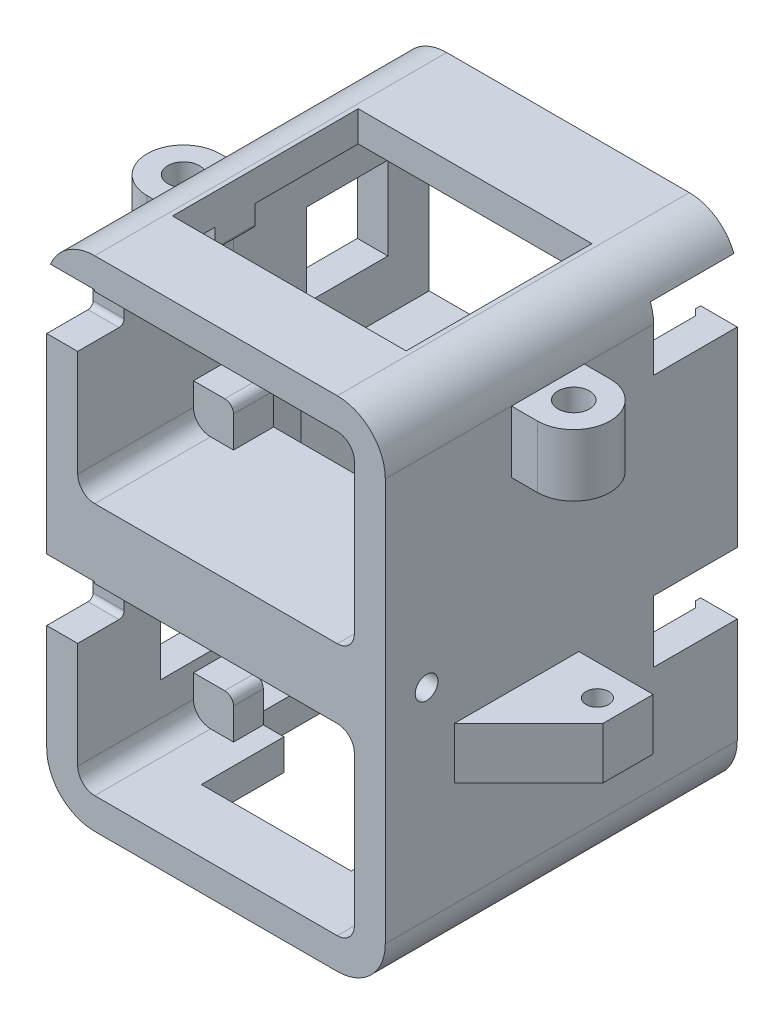
SolidWorks part; units mm, degrees
ref_plane "前视基准面" through (0, 0, 0) normal (0, 0, 1) x (1, 0, 0)
ref_plane "上视基准面" through (0, 0, 0) normal (0, 1, 0) x (1, 0, 0)
ref_plane "右视基准面" through (0, 0, 0) normal (1, 0, 0) x (0, 0, -1)
other "Configuration Table"
sketch "草图2" plane through (0, 0, 0) normal (0, 0, 1) x (1, 0, 0)
  line L20 (13.4, -7.25) -> (13.4, 7.25)
  line L21 (11.75, 8.9) -> (-16.9, 8.9)
  line L22 (-16.9, 8.9) -> (-16.9, 3.2)
  line L23 (-16.9, 3.2) -> (-13.4, 3.2)
  line L24 (-13.4, 3.2) -> (-13.4, -7.25)
  line L25 (-11.75, -8.9) -> (-3.85, -8.9)
  line L26 (-3.85, -8.9) -> (-3.85, -7.9)
  line L27 (-3.85, -7.9) -> (3.85, -7.9)
  line L28 (3.85, -7.9) -> (3.85, -8.9)
  line L29 (3.85, -8.9) -> (11.75, -8.9)
  line L40 (13.4, -7.25) -> (13.4, 7.25)
  line L41 (11.75, 8.9) -> (-16.9, 8.9)
  line L42 (-16.9, 8.9) -> (-16.9, 3.2)
  line L43 (-16.9, 3.2) -> (-13.4, 3.2)
  line L44 (-13.4, 3.2) -> (-13.4, -7.25)
  line L45 (-11.75, -8.9) -> (-3.85, -8.9)
  line L49 (3.85, -8.9) -> (11.75, -8.9)
  line L50 (-3.85, 15.6) -> (3.85, 15.6)
  line L51 (-3.85, -8.9) -> (3.85, -8.9)
  line L52 (-3.85, 12.6) -> (3.85, 12.6)
  line L53 (3.85, 12.6) -> (11.75, 12.6)
  line L54 (16.4, 17.25) -> (16.4, 31.75)
  line L55 (11.75, 36.4) -> (-19.9, 36.4)
  line L56 (-19.9, 36.4) -> (-19.9, 24.7)
  line L57 (-19.9, 24.7) -> (-16.4, 24.7)
  line L58 (-16.4, 24.7) -> (-16.4, 17.25)
  line L59 (-11.75, 12.6) -> (-3.85, 12.6)
  line L70 (13.4, 17.25) -> (13.4, 31.75)
  line L71 (11.75, 33.4) -> (-16.9, 33.4)
  line L72 (-16.9, 33.4) -> (-16.9, 27.7)
  line L73 (-16.9, 27.7) -> (-13.4, 27.7)
  line L74 (-13.4, 27.7) -> (-13.4, 17.25)
  line L75 (-11.75, 15.6) -> (-3.85, 15.6)
  line L76 (-3.85, 15.6) -> (-3.85, 16.6)
  line L77 (-3.85, 16.6) -> (3.85, 16.6)
  line L78 (3.85, 16.6) -> (3.85, 15.6)
  line L79 (3.85, 15.6) -> (11.75, 15.6)
  line L80 (13.4, 17.25) -> (13.4, 31.75)
  line L81 (11.75, 33.4) -> (-16.9, 33.4)
  line L82 (-16.9, 33.4) -> (-16.9, 27.7)
  line L83 (-16.9, 27.7) -> (-13.4, 27.7)
  line L84 (-13.4, 27.7) -> (-13.4, 17.25)
  line L85 (-11.75, 15.6) -> (-3.85, 15.6)
  line L89 (3.85, 15.6) -> (11.75, 15.6)
  line L90 (16.4, -7.25) -> (16.4, 7.25)
  line L91 (11.75, 11.9) -> (-19.9, 11.9)
  line L92 (-19.9, 11.9) -> (-19.9, 0.2)
  line L93 (-19.9, 0.2) -> (-16.4, 0.2)
  line L94 (-16.4, 0.2) -> (-16.4, -7.25)
  line L95 (-11.75, -11.9) -> (-3.85, -11.9)
  line L96 (-3.85, -11.9) -> (3.85, -11.9)
  line L97 (3.85, -11.9) -> (11.75, -11.9)
  line L98 (-16.4, 0.2) -> (-16.4, 3.2)
  line L99 (-16.4, 17.25) -> (-16.4, 11.9)
  line L100 (16.4, 17.25) -> (16.4, 7.25)
  line L101 (-16.9, 33.4) -> (-19.9, 33.4)
  line L102 (-16.9, 27.7) -> (-19.9, 27.7)
  line L103 (-16.9, 8.9) -> (-19.9, 8.9)
  line L104 (-16.4, 24.7) -> (-16.4, 27.7)
  line L105 (-16.4, 36.4) -> (-16.4, 33.4)
  line L106 (-16.4, 11.9) -> (-16.4, 8.9)
  line L107 (-16.4, 33.4) -> (-16.4, 27.7)
  line L108 (-16.4, 8.9) -> (-16.4, 3.2)
  line L109 (-13.4, 27.7) -> (-13.4, 33.4)
  line L110 (-13.4, 3.2) -> (-13.4, 8.9)
  arc A1 (-11.75, 11.9) -> (-16.4, 7.25) centre (-11.75, 7.25) ccw
  arc A2 (-11.75, 8.9) -> (-13.4, 7.25) centre (-11.75, 7.25) ccw
  arc A3 (-11.75, 8.9) -> (-13.4, 7.25) centre (-11.75, 7.25) ccw
  arc A6 (13.4, 7.25) -> (11.75, 8.9) centre (11.75, 7.25) ccw
  arc A7 (-13.4, -7.25) -> (-11.75, -8.9) centre (-11.75, -7.25) ccw
  arc A8 (11.75, -8.9) -> (13.4, -7.25) centre (11.75, -7.25) ccw
  arc A12 (13.4, 7.25) -> (11.75, 8.9) centre (11.75, 7.25) ccw
  arc A13 (-13.4, -7.25) -> (-11.75, -8.9) centre (-11.75, -7.25) ccw
  arc A14 (11.75, -8.9) -> (13.4, -7.25) centre (11.75, -7.25) ccw
  arc A15 (11.75, 12.6) -> (16.4, 17.25) centre (11.75, 17.25) ccw
  arc A16 (16.4, 31.75) -> (11.75, 36.4) centre (11.75, 31.75) ccw
  arc A17 (-16.4, 17.25) -> (-11.75, 12.6) centre (-11.75, 17.25) ccw
  arc A21 (13.4, 31.75) -> (11.75, 33.4) centre (11.75, 31.75) ccw
  arc A22 (-13.4, 17.25) -> (-11.75, 15.6) centre (-11.75, 17.25) ccw
  arc A23 (11.75, 15.6) -> (13.4, 17.25) centre (11.75, 17.25) ccw
  arc A24 (13.4, 31.75) -> (11.75, 33.4) centre (11.75, 31.75) ccw
  arc A25 (-13.4, 17.25) -> (-11.75, 15.6) centre (-11.75, 17.25) ccw
  arc A26 (11.75, 15.6) -> (13.4, 17.25) centre (11.75, 17.25) ccw
  arc A27 (16.4, 7.25) -> (11.75, 11.9) centre (11.75, 7.25) ccw
  arc A28 (-16.4, -7.25) -> (-11.75, -11.9) centre (-11.75, -7.25) ccw
  arc A29 (11.75, -11.9) -> (16.4, -7.25) centre (11.75, -7.25) ccw
  arc A31 (-11.75, 36.4) -> (-16.4, 31.75) centre (-11.75, 31.75) ccw
  arc A32 (-11.75, 33.4) -> (-13.4, 31.75) centre (-11.75, 31.75) ccw
  arc A33 (-11.75, 33.4) -> (-13.4, 31.75) centre (-11.75, 31.75) ccw
  dimension "D3" = 3
  dimension "D4" = 3
  dimension "D5" = 0.1
  dimension "D6" = 3
  dimension "D7" = 0.1
  dimension "D8" = 3
extrude "凸台-拉伸2" add sketch "草图2" against normal up to surface (11.22 mm away)
sketch "草图3" plane through (0, 0, -11.22) normal (0, 0, -1) x (-1, 0, 0)
  line L0 (11.75, -8.9) -> (-11.75, -8.9) construction
  line L2 (-11.75, 8.9) -> (11.75, 8.9) construction
  line L3 (11.75, -8.9) -> (-11.75, -8.9)
  line L4 (16.4, -7.25) -> (16.4, 31.75)
  line L5 (11.75, 36.4) -> (-11.75, 36.4)
  line L6 (-16.4, 31.75) -> (-16.4, -7.25)
  line L7 (-11.75, -11.9) -> (11.75, -11.9)
  line L12 (16.4, -7.25) -> (16.4, 31.75)
  line L13 (11.75, 36.4) -> (-11.75, 36.4)
  line L14 (-16.4, 31.75) -> (-16.4, -7.25)
  line L16 (-11.75, -11.9) -> (11.75, -11.9)
  line L20 (-13.4, -7.25) -> (-13.4, 7.25)
  line L21 (-11.75, 33.4) -> (11.75, 33.4) construction
  line L22 (-13.4, 17.25) -> (-13.4, 31.75) construction
  line L23 (-9.52, -8.6) -> (-9.52, -5.87)
  line L24 (-10.37, -5.02) -> (-13.1, -5.02)
  line L25 (-13.1, -5.02) -> (-13.1, -7.25)
  line L26 (-11.75, -8.6) -> (-9.52, -8.6)
  line L27 (-9.52, -8.6) -> (-9.52, -5.87)
  line L28 (-10.37, -5.02) -> (-13.1, -5.02)
  line L32 (11.75, 15.6) -> (-11.75, 15.6) construction
  line L33 (-11.75, 33.4) -> (11.75, 33.4)
  line L34 (-13.4, 17.25) -> (-13.4, 31.75)
  line L36 (11.75, 15.6) -> (-11.75, 15.6)
  line L38 (13.4, 7.25) -> (13.4, -7.25) construction
  line L39 (13.1, -5.02) -> (10.37, -5.02)
  line L40 (9.52, -5.87) -> (9.52, -8.6)
  line L41 (9.52, -8.6) -> (11.75, -8.6)
  line L42 (13.1, -7.25) -> (13.1, -5.02)
  line L43 (13.1, -5.02) -> (10.37, -5.02)
  line L44 (9.52, -5.87) -> (9.52, -8.6)
  line L47 (13.4, 7.25) -> (13.4, -7.25)
  line L48 (-11.75, 8.9) -> (11.75, 8.9) construction
  line L49 (-9.52, 15.75) -> (-9.52, 18.63)
  line L50 (-10.37, 19.48) -> (-13.25, 19.48)
  line L51 (-13.1, 6.82) -> (-11.67, 6.82)
  line L52 (-11.32, 7.17) -> (-11.32, 8.6)
  line L53 (-11.32, 8.6) -> (-11.75, 8.6)
  line L54 (-13.1, 7.25) -> (-13.1, 6.82)
  line L55 (-13.1, 6.82) -> (-11.67, 6.82)
  line L56 (-11.32, 7.17) -> (-11.32, 8.6)
  line L59 (-13.1, 6.82) -> (-13.4, 6.82)
  line L60 (-13.4, -7.25) -> (-13.4, 7.25) construction
  line L61 (-9.52, 15.6) -> (-9.52, 18.63)
  line L62 (-10.37, 19.48) -> (-13.4, 19.48)
  line L63 (11.32, 8.6) -> (11.32, 7.17)
  line L64 (11.67, 6.82) -> (13.1, 6.82)
  line L65 (13.1, 6.82) -> (13.1, 7.25)
  line L66 (11.75, 8.6) -> (11.32, 8.6)
  line L67 (11.32, 8.9) -> (11.32, 7.17)
  line L68 (11.67, 6.82) -> (13.4, 6.82)
  line L71 (-11.75, 8.9) -> (11.75, 8.9)
  line L73 (-13.25, 31.32) -> (-11.67, 31.32)
  line L74 (-11.32, 31.67) -> (-11.32, 33.25)
  line L75 (-13.25, 31.32) -> (-11.67, 31.32)
  line L76 (-11.32, 31.67) -> (-11.32, 33.25)
  line L79 (11.67, 31.32) -> (13.25, 31.32)
  line L80 (11.32, 33.25) -> (11.32, 31.67)
  line L81 (11.67, 31.32) -> (13.4, 31.32)
  line L82 (11.32, 33.25) -> (11.32, 31.67)
  line L83 (-13.25, 31.32) -> (-13.4, 31.32)
  line L84 (-11.32, 33.25) -> (-11.32, 33.4)
  line L85 (9.52, 18.63) -> (9.52, 15.75)
  line L86 (13.25, 19.48) -> (10.37, 19.48)
  line L87 (9.52, 18.63) -> (9.52, 15.6)
  line L88 (13.4, 19.48) -> (10.37, 19.48)
  line L89 (11.32, 33.25) -> (11.32, 33.4)
  line L90 (-11.32, 8.6) -> (-11.32, 8.9)
  line L91 (13.4, 31.75) -> (13.4, 17.25) construction
  line L92 (13.4, 31.75) -> (13.4, 17.25)
  line L93 (-13.1, -5.02) -> (-13.4, -5.02)
  line L94 (-9.52, -8.6) -> (-9.52, -8.9)
  line L95 (9.52, -8.6) -> (9.52, -8.9)
  line L96 (13.1, -5.02) -> (13.4, -5.02)
  arc A0 (-13.4, -7.25) -> (-11.75, -8.9) centre (-11.75, -7.25) ccw construction
  arc A1 (11.75, -8.9) -> (13.4, -7.25) centre (11.75, -7.25) ccw construction
  arc A2 (-11.75, 8.9) -> (-13.4, 7.25) centre (-11.75, 7.25) ccw construction
  arc A3 (11.75, -11.9) -> (16.4, -7.25) centre (11.75, -7.25) ccw
  arc A4 (-11.75, 36.4) -> (-16.4, 31.75) centre (-11.75, 31.75) ccw
  arc A5 (-16.4, -7.25) -> (-11.75, -11.9) centre (-11.75, -7.25) ccw
  arc A6 (11.75, -11.9) -> (16.4, -7.25) centre (11.75, -7.25) ccw
  arc A9 (-11.75, 36.4) -> (-16.4, 31.75) centre (-11.75, 31.75) ccw
  arc A10 (-9.52, -5.87) -> (-10.37, -5.02) centre (-10.37, -5.87) ccw
  arc A11 (-13.1, -7.25) -> (-11.75, -8.6) centre (-11.75, -7.25) ccw
  arc A12 (-9.52, -5.87) -> (-10.37, -5.02) centre (-10.37, -5.87) ccw
  arc A14 (-16.4, -7.25) -> (-11.75, -11.9) centre (-11.75, -7.25) ccw
  arc A15 (-13.4, -7.25) -> (-11.75, -8.9) centre (-11.75, -7.25) ccw
  arc A16 (11.75, -8.9) -> (13.4, -7.25) centre (11.75, -7.25) ccw
  arc A17 (-11.75, 8.9) -> (-13.4, 7.25) centre (-11.75, 7.25) ccw
  arc A18 (10.37, -5.02) -> (9.52, -5.87) centre (10.37, -5.87) ccw
  arc A19 (11.75, -8.6) -> (13.1, -7.25) centre (11.75, -7.25) ccw
  arc A20 (10.37, -5.02) -> (9.52, -5.87) centre (10.37, -5.87) ccw
  arc A22 (-11.75, 33.4) -> (-13.4, 31.75) centre (-11.75, 31.75) ccw construction
  arc A23 (11.75, 15.6) -> (13.4, 17.25) centre (11.75, 17.25) ccw construction
  arc A24 (-11.67, 6.82) -> (-11.32, 7.17) centre (-11.67, 7.17) ccw
  arc A25 (-11.75, 8.6) -> (-13.1, 7.25) centre (-11.75, 7.25) ccw
  arc A26 (-11.67, 6.82) -> (-11.32, 7.17) centre (-11.67, 7.17) ccw
  arc A28 (-13.4, 17.25) -> (-11.75, 15.6) centre (-11.75, 17.25) ccw construction
  arc A29 (-11.75, 33.4) -> (-13.4, 31.75) centre (-11.75, 31.75) ccw
  arc A30 (11.32, 7.17) -> (11.67, 6.82) centre (11.67, 7.17) ccw
  arc A31 (13.1, 7.25) -> (11.75, 8.6) centre (11.75, 7.25) ccw
  arc A32 (11.32, 7.17) -> (11.67, 6.82) centre (11.67, 7.17) ccw
  arc A34 (11.75, 15.6) -> (13.4, 17.25) centre (11.75, 17.25) ccw
  arc A35 (-13.4, 17.25) -> (-11.75, 15.6) centre (-11.75, 17.25) ccw
  arc A36 (13.4, 7.25) -> (11.75, 8.9) centre (11.75, 7.25) ccw construction
  arc A37 (13.4, 7.25) -> (11.75, 8.9) centre (11.75, 7.25) ccw
  arc A38 (-9.52, 18.63) -> (-10.37, 19.48) centre (-10.37, 18.63) ccw
  arc A39 (-9.52, 18.63) -> (-10.37, 19.48) centre (-10.37, 18.63) ccw
  arc A41 (-11.67, 31.32) -> (-11.32, 31.67) centre (-11.67, 31.67) ccw
  arc A42 (-11.67, 31.32) -> (-11.32, 31.67) centre (-11.67, 31.67) ccw
  arc A44 (11.32, 31.67) -> (11.67, 31.32) centre (11.67, 31.67) ccw
  arc A45 (11.32, 31.67) -> (11.67, 31.32) centre (11.67, 31.67) ccw
  arc A46 (13.4, 31.75) -> (11.75, 33.4) centre (11.75, 31.75) ccw construction
  arc A47 (10.37, 19.48) -> (9.52, 18.63) centre (10.37, 18.63) ccw
  arc A48 (10.37, 19.48) -> (9.52, 18.63) centre (10.37, 18.63) ccw
  arc A49 (13.4, 31.75) -> (11.75, 33.4) centre (11.75, 31.75) ccw
  arc A52 (16.4, 31.75) -> (11.75, 36.4) centre (11.75, 31.75) ccw
  arc A53 (16.4, 31.75) -> (11.75, 36.4) centre (11.75, 31.75) ccw
  dimension "D7" = 0.1
  dimension "D9" = 0.1
extrude "凸台-拉伸3" add sketch "草图3" along normal up to surface (3.88 mm away)
sketch "草图4" plane through (-16.4, 0, 0) normal (-1, 0, 0) x (0, 0, 1)
  line L8 (0.3, 9.05) -> (-4, 9.05)
  line L9 (-4.5, 8.55) -> (-4.5, 3.55)
  line L10 (-4, 3.05) -> (0.3, 3.05)
  line L11 (0.3, 3.05) -> (0.3, 9.05)
  line L12 (0.3, 9.05) -> (-4, 9.05)
  line L13 (-4.5, 8.55) -> (-4.5, 3.55)
  line L14 (-4, 3.05) -> (0.3, 3.05)
  line L15 (0.3, 3.05) -> (0.3, 9.05)
  line L20 (0.3, 33.55) -> (-4, 33.55)
  line L21 (-4.5, 33.05) -> (-4.5, 28.05)
  line L22 (-4, 27.55) -> (0.3, 27.55)
  line L23 (0.3, 27.55) -> (0.3, 33.55)
  line L24 (0.3, 33.55) -> (-4, 33.55)
  line L25 (-4.5, 33.05) -> (-4.5, 28.05)
  line L26 (-4, 27.55) -> (0.3, 27.55)
  line L27 (0.3, 27.55) -> (0.3, 33.55)
  arc A4 (-4, 9.05) -> (-4.5, 8.55) centre (-4, 8.55) ccw
  arc A5 (-4.5, 3.55) -> (-4, 3.05) centre (-4, 3.55) ccw
  arc A6 (-4, 9.05) -> (-4.5, 8.55) centre (-4, 8.55) ccw
  arc A7 (-4.5, 3.55) -> (-4, 3.05) centre (-4, 3.55) ccw
  arc A10 (-4, 33.55) -> (-4.5, 33.05) centre (-4, 33.05) ccw
  arc A11 (-4.5, 28.05) -> (-4, 27.55) centre (-4, 28.05) ccw
  arc A12 (-4, 33.55) -> (-4.5, 33.05) centre (-4, 33.05) ccw
  arc A13 (-4.5, 28.05) -> (-4, 27.55) centre (-4, 28.05) ccw
  dimension "D2" = 0.15
  dimension "D1" = 0.15
extrude "切除-拉伸1" cut sketch "草图4" against normal blind 4.65
ref_plane "基准面1" through (0, 31.75, 0) normal (0, 1, 0) x (1, 0, 0)
sketch "草图8" plane through (0, 31.75, 0) normal (0, 1, 0) x (1, 0, 0)
  line L0 (18.9, 12.23) -> (15.375, 12.23)
  line L1 (15.375, 12.23) -> (15.375, 15.755)
  line L2 (16.4, 15.1) -> (16.4, 0) construction
  line L3 (-12.113, 15.755) -> (15.375, 15.755) construction
  line L4 (9.73, 15.91) -> (-9.73, 15.91) construction
  line L5 (-9.73, 15.6) -> (9.73, 15.6) construction
  line L9 (18.9, 19.28) -> (15.375, 19.28)
  line L10 (15.375, 15.755) -> (15.375, 19.28)
  circle A2 centre (18.9, 15.755) radius 1.525
  circle A3 centre (18.9, 15.755) radius 3.525
  point P16 (18.9, 19.28)
  point P17 (15.2716, 15.755)
  dimension "D1" = 3.05
  dimension "D3" = 2.5
  dimension "D2" = 2
extrude "凸台-拉伸5" add sketch "草图8" against normal blind 6 contours A3 A2 | A3 L9 L10 | A3 L1 L0
mirror "镜向1" about plane through (0, 0, 0) normal (1, 0, 0) of "凸台-拉伸5"
sketch "草图9" plane through (0, 0, -15.1) normal (0, 0, -1) x (-1, 0, 0)
  line L0 (-11.32, 33.4) -> (11.32, 33.4) construction
  line L1 (-11.32, 33.4) -> (11.32, 33.4)
  line L2 (-11.32, 33.4) -> (-11.32, 36.4)
  line L3 (-11.32, 36.4) -> (11.32, 36.4)
  line L4 (11.32, 33.4) -> (11.32, 36.4)
  line L5 (11.75, 36.4) -> (-11.75, 36.4) construction
  line L6 (-11.32, 31.67) -> (-11.32, 33.4) construction
  line L7 (11.32, 33.4) -> (11.32, 31.67) construction
extrude "切除-拉伸3" cut sketch "草图9" against normal blind 8
sketch "草图10" plane through (0, 0, -15.1) normal (0, 0, -1) x (-1, 0, 0)
  line L0 (-11.75, -11.9) -> (11.75, -11.9) construction
  line L1 (-10.73, -11.9) -> (10.73, -11.9)
  line L2 (-10.73, -11.9) -> (-10.73, -5.02)
  line L3 (-10.73, -5.02) -> (10.73, -5.02)
  line L4 (10.73, -11.9) -> (10.73, -5.02)
  line L5 (13.4, -5.02) -> (10.37, -5.02) construction
  line L6 (-9.73, 23.6695) -> (-9.73, 22.7695) construction
  line L7 (9.73, 71.4195) -> (9.73, -46.2805) construction
  dimension "D1" = 1
  dimension "D2" = 1
extrude "切除-拉伸4" cut sketch "草图10" against normal blind 1
sketch "草图12" plane through (-16.4, 0, 0) normal (-1, 0, 0) x (0, 0, 1)
  circle A0 centre (-4, 12.25) radius 1.1
  dimension "D1" = 2.2
extrude "切除-拉伸5" cut sketch "草图12" against normal blind 8
sketch "草图13" plane through (16.4, 0, 0) normal (1, 0, 0) x (0, 0, -1)
  circle A0 centre (4, 12.25) radius 1.1
  dimension "D1" = 2.2
extrude "切除-拉伸6" cut sketch "草图13" against normal blind 8
sketch "草图14" plane through (0, 0, -15.1) normal (0, 0, -1) x (-1, 0, 0)
  line L0 (-9.52, 18.63) -> (-16.4, 18.63)
  line L1 (-10.37, 19.48) -> (-13.4, 19.48) construction
  line L2 (-16.4, 8.95) -> (16.4, 8.95)
  line L3 (-9.52, 18.63) -> (16.4, 18.63)
  line L4 (-11.32, 8.9) -> (11.32, 8.9) construction
  line L6 (9.88, -46.4305) -> (9.88, 71.4899)
  line L7 (-9.88, -46.4305) -> (9.88, -46.4305)
  line L8 (-9.88, 71.4899) -> (-9.88, -46.4305)
  line L9 (9.88, -46.4305) -> (9.88, 71.4899)
  line L10 (-9.88, -46.4305) -> (9.88, -46.4305)
  line L11 (-9.88, 71.4899) -> (-9.88, -46.4305)
  line L19 (16.4, 3.05) -> (13.4, 3.05)
  line L20 (16.4, -7.25) -> (16.4, 3.05)
  line L21 (-11.75, -11.9) -> (11.75, -11.9)
  line L22 (-16.4, 31.75) -> (-16.4, -7.25)
  line L23 (11.75, 36.4) -> (-11.75, 36.4)
  line L24 (11.75, 33.55) -> (16.0375, 33.55)
  line L25 (11.75, 33.4) -> (11.75, 33.55)
  line L26 (-11.75, 33.4) -> (11.75, 33.4)
  line L27 (-13.4, 17.25) -> (-13.4, 31.75)
  line L28 (11.75, 15.6) -> (-11.75, 15.6)
  line L29 (13.4, 27.55) -> (13.4, 17.25)
  line L30 (16.4, 27.55) -> (13.4, 27.55)
  line L31 (16.4, 9.05) -> (16.4, 27.55)
  line L32 (11.75, 9.05) -> (16.4, 9.05)
  line L33 (11.75, 8.9) -> (11.75, 9.05)
  line L34 (-11.75, 8.9) -> (11.75, 8.9)
  line L35 (-13.4, -7.25) -> (-13.4, 7.25)
  line L36 (11.75, -8.9) -> (-11.75, -8.9)
  line L37 (13.4, 3.05) -> (13.4, -7.25)
  line L39 (16.4, -7.25) -> (16.4, 9.05)
  line L40 (-11.75, -11.9) -> (11.75, -11.9)
  line L41 (-16.4, 31.75) -> (-16.4, -7.25)
  line L42 (11.75, 36.4) -> (-11.75, 36.4)
  line L50 (16.4, 9.05) -> (16.4, 31.75)
  arc A2 (9.88, 71.4899) -> (-9.88, 71.4899) centre (0, 59.6448) ccw
  arc A3 (9.88, 71.4899) -> (-9.88, 71.4899) centre (0, 59.6448) ccw
  arc A10 (11.75, -11.9) -> (16.4, -7.25) centre (11.75, -7.25) ccw
  arc A11 (-16.4, -7.25) -> (-11.75, -11.9) centre (-11.75, -7.25) ccw
  arc A12 (-11.75, 36.4) -> (-16.4, 31.75) centre (-11.75, 31.75) ccw
  arc A13 (16.0375, 33.55) -> (11.75, 36.4) centre (11.75, 31.75) ccw
  arc A14 (-11.75, 33.4) -> (-13.4, 31.75) centre (-11.75, 31.75) ccw
  arc A15 (-13.4, 17.25) -> (-11.75, 15.6) centre (-11.75, 17.25) ccw
  arc A16 (11.75, 15.6) -> (13.4, 17.25) centre (11.75, 17.25) ccw
  arc A17 (-11.75, 8.9) -> (-13.4, 7.25) centre (-11.75, 7.25) ccw
  arc A18 (-13.4, -7.25) -> (-11.75, -8.9) centre (-11.75, -7.25) ccw
  arc A19 (11.75, -8.9) -> (13.4, -7.25) centre (11.75, -7.25) ccw
  arc A20 (11.75, -11.9) -> (16.4, -7.25) centre (11.75, -7.25) ccw
  arc A21 (-16.4, -7.25) -> (-11.75, -11.9) centre (-11.75, -7.25) ccw
  arc A22 (-11.75, 36.4) -> (-16.4, 31.75) centre (-11.75, 31.75) ccw
  arc A23 (16.4, 31.75) -> (11.75, 36.4) centre (11.75, 31.75) ccw
  line M49 (16.4, -7.25) -> (16.4, 25.75)
  line M75 (-16.4, 25.75) -> (-16.4, -7.25)
  dimension "D4" = 0.05
  dimension "D3" = 0.85
  dimension "D2" = 0.15
extrude "凸台-拉伸7" add sketch "草图14" along normal blind 3 contours L11 L0 L2 M75 | L9 L2 L3 M49
sketch "草图15" plane through (0, 0, -15.1) normal (0, 0, -1) x (-1, 0, 0)
  line L0 (-9.52, -8.9) -> (9.52, -8.9) construction
  line L1 (-16.4, 18.63) -> (-16.4, 8.95) construction
  line L3 (-16.4, 18.63) -> (-16.4, 8.95)
  line L5 (16.4, 8.95) -> (16.4, 18.63) construction
  line L13 (16.4, 8.95) -> (16.4, 18.63)
  line L24 (-11.75, 36.4) -> (11.75, 36.4)
  line L25 (-16.4, 25.75) -> (-16.4, 18.63) construction
  line L26 (-16.4, 25.75) -> (-16.4, 18.63)
  line L27 (-16.4, 8.95) -> (-16.4, -7.25) construction
  line L28 (-16.4, 8.95) -> (-16.4, -7.25)
  line L29 (-16.4, 25.75) -> (-16.4, 31.75)
  line L31 (-11.75, -11.9) -> (11.75, -11.9)
  line L32 (-11.32, 33.4) -> (11.32, 33.4) construction
  line L33 (-13.45, 33.45) -> (13.45, 33.45)
  line L34 (-13.45, 33.45) -> (-13.45, -8.95)
  line L35 (-13.45, -8.95) -> (13.45, -8.95)
  line L36 (13.45, 33.45) -> (13.45, -8.95)
  line L37 (-13.4, 19.48) -> (-13.4, 31.32) construction
  line L39 (13.4, 31.32) -> (13.4, 19.48) construction
  line L40 (16.4, -7.25) -> (16.4, 8.95)
  line L41 (16.4, 18.63) -> (16.4, 31.75)
  line L46 (16.4, 15.5) -> (16.4, 9)
  arc A0 (16.4, 31.75) -> (11.75, 36.4) centre (11.75, 31.75) ccw construction
  arc A1 (-11.75, 36.4) -> (-16.4, 31.75) centre (-11.75, 31.75) ccw construction
  arc A2 (16.4, 31.75) -> (11.75, 36.4) centre (11.75, 31.75) ccw
  arc A3 (-11.75, 36.4) -> (-16.4, 31.75) centre (-11.75, 31.75) ccw
  arc A4 (-16.4, -7.25) -> (-11.75, -11.9) centre (-11.75, -7.25) ccw construction
  arc A5 (-16.4, -7.25) -> (-11.75, -11.9) centre (-11.75, -7.25) ccw
  arc A6 (11.75, -11.9) -> (16.4, -7.25) centre (11.75, -7.25) ccw construction
  arc A7 (11.75, -11.9) -> (16.4, -7.25) centre (11.75, -7.25) ccw
  point P2 (0, 0)
  dimension "D1" = 0.05
  dimension "D2" = 0.05
  dimension "D4" = 0.05
  dimension "D3" = 0.05
extrude "凸台-拉伸8" add sketch "草图15" along normal blind 19
sketch "草图16" plane through (0, 0, -18.1) normal (0, 0, -1) x (-1, 0, 0)
  line L0 (-13.45, 33.45) -> (-13.45, -8.95) construction
  line L1 (-13.45, 8.95) -> (13.45, 8.95)
  line L2 (-13.45, 8.95) -> (-13.45, 15.55)
  line L3 (-13.45, 15.55) -> (13.45, 15.55)
  line L4 (13.45, 8.95) -> (13.45, 15.55)
  line L5 (13.45, 33.45) -> (13.45, -8.95) construction
  line L6 (-11.32, 8.9) -> (11.32, 8.9) construction
  line L7 (9.52, 15.6) -> (-9.52, 15.6) construction
  dimension "D1" = 0.05
  dimension "D2" = 0.05
extrude "凸台-拉伸9" add sketch "草图16" along normal up to surface (16 mm away)
sketch "草图11" plane through (0, 2.8903, 0) normal (0, 1, 0) x (1, 0, 0)
  line L1 (16.4, 34.1) -> (16.4, 0) construction
  line L2 (16.4, 34.1) -> (16.4, 0)
  line L7 (18.8958, 21.655) -> (18.8958, 16.405)
  line L8 (18.8958, 16.405) -> (20.4358, 16.405)
  line L9 (20.4358, 15.105) -> (18.8958, 15.105)
  line L10 (18.8958, 15.105) -> (18.8958, 9.855)
  line L11 (18.8958, 9.855) -> (23.5958, 9.855)
  line L12 (23.5958, 9.855) -> (23.5958, 21.655)
  line L13 (23.5958, 21.655) -> (18.8958, 21.655)
  line L19 (23.5958, 13.9124) -> (23.5958, 18.755)
  line L21 (16.4, 18.755) -> (23.5958, 18.755)
  line L22 (23.5958, 13.9124) -> (16.4, 6.7166)
  circle A0 centre (21.1958, 15.755) radius 1.1
  arc A1 (20.4358, 15.105) -> (20.4358, 16.405) centre (21.1958, 15.755) ccw
  point P9 (23.5958, 13.7436)
  point P12 (16.4, 18.8542)
  line M15 (18.8958, 21.655) -> (18.8958, 16.405)
  line M16 (18.8958, 16.405) -> (20.4358, 16.405)
  line M18 (20.4358, 15.105) -> (18.8958, 15.105)
  line M19 (18.8958, 15.105) -> (18.8958, 9.855)
  line M20 (18.8958, 9.855) -> (23.5958, 9.855)
  line M21 (23.5958, 9.855) -> (23.5958, 21.655)
  dimension "D6" = 2.2
  dimension "D2" = 3
  dimension "D5" = 45
  dimension "D7" = 3
  dimension "D1" = 0
extrude "凸台-拉伸6" add sketch "草图11" along normal blind 5 contours A0 L21 L2 L22 M16 M15 M20 M19 M18 | A0 L22 L21 M18 M19 M20 M21 M15 M16
sketch "草图17" plane through (0, 8.95, 0) normal (0, -1, 0) x (1, 0, 0)
  line L0 (-9.88, -18.1) -> (0, -27.98)
  line L1 (0, -27.98) -> (9.88, -18.1)
  line L2 (9.88, -18.1) -> (-9.88, -18.1) construction
  line L3 (-9.88, -18.1) -> (9.88, -18.1)
  dimension "D1" = 45
  dimension "D2" = 45
extrude "切除-拉伸8" cut sketch "草图17" against normal up to next
sketch "草图18" plane through (13.45, 0, 0) normal (-1, 0, 0) x (0, 0, 1)
  line L0 (0, -7.25) -> (0, 31.75) construction
  line L1 (-34.1, 2.95) -> (-26, 2.95)
  line L2 (-34.1, 2.95) -> (-34.1, 8.95)
  line L3 (-34.1, 8.95) -> (-26, 8.95)
  line L4 (-26, 2.95) -> (-26, 8.95)
  line L5 (-34.1, 27.45) -> (-26, 27.45)
  line L6 (-34.1, 27.45) -> (-34.1, 33.45)
  line L7 (-34.1, 33.45) -> (-26, 33.45)
  line L8 (-26, 27.45) -> (-26, 33.45)
  dimension "D2" = 6
  dimension "D3" = 6
  dimension "D5" = 26
extrude "切除-拉伸9" cut sketch "草图18" against normal up to next
sketch "草图19" plane through (0, -11.9, 0) normal (0, -1, 0) x (1, 0, 0)
  line L1 (-10.73, -14.1) -> (10.73, -14.1)
  line L2 (-10.73, -14.1) -> (-10.73, -15.1)
  line L3 (-10.73, -15.1) -> (10.73, -15.1)
  line L4 (10.73, -14.1) -> (10.73, -15.1)
  line L5 (-10.73, -15.1) -> (10.73, -15.1)
  line L6 (-10.73, -15.1) -> (-10.73, -25.1)
  line L7 (-10.73, -25.1) -> (10.73, -25.1)
  line L8 (10.73, -15.1) -> (10.73, -25.1)
  line M10 (10.73, -14.1) -> (10.73, -15.1)
  line M11 (10.73, -15.1) -> (-10.73, -15.1)
  line M12 (-10.73, -15.1) -> (-10.73, -14.1)
  line M13 (-10.73, -14.1) -> (10.73, -14.1)
  dimension "D1" = 10
extrude "切除-拉伸10" cut sketch "草图19" against normal up to next contours M10 M13 M12 M11 | L8 L6 L7 M11
sketch "草图24" plane through (0, -11.9, 0) normal (0, -1, 0) x (1, 0, 0)
  line L0 (9.52, -14.1) -> (-9.52, -14.1) construction
  line L1 (9.52, -14.1) -> (-9.52, -14.1)
  line L3 (-7, -6.1) -> (7, -6.1)
  line L4 (-7, -6.1) -> (-7, -14.1)
  line L5 (-7, -14.1) -> (7, -14.1)
  line L6 (7, -6.1) -> (7, -14.1)
  line L7 (-7, -6.1) -> (7, -14.1) construction
  line L8 (-7, -14.1) -> (7, -6.1) construction
  point P2 (0, -10.1)
  dimension "D1" = 8
  dimension "D2" = 14
extrude "切除-拉伸14" cut sketch "草图24" against normal up to next contours L6 L3 L4 L1
sketch "草图20" plane through (0, 36.4, 0) normal (0, 1, 0) x (1, 0, 0)
  line L1 (-11.32, 15.1) -> (11.32, 15.1)
  line L2 (-11.32, 15.1) -> (-11.32, 25.1)
  line L3 (-11.32, 25.1) -> (11.32, 25.1)
  line L4 (11.32, 15.1) -> (11.32, 25.1)
  dimension "D1" = 10
extrude "切除-拉伸11" cut sketch "草图20" against normal up to next
sketch "草图21" plane through (13.45, 0, 0) normal (-1, 0, 0) x (0, 0, 1)
  line L6 (-34.1, 27.45) -> (-32.6, 27.45)
  line L7 (-34.1, 27.45) -> (-34.1, 22.45)
  line L8 (-34.1, 22.45) -> (-32.6, 22.45)
  line L9 (-32.6, 27.45) -> (-32.6, 22.45)
  line L10 (-34.1, 2.95) -> (-32.6, 2.95)
  line L11 (-34.1, 2.95) -> (-34.1, -2.05)
  line L12 (-34.1, -2.05) -> (-32.6, -2.05)
  line L13 (-32.6, 2.95) -> (-32.6, -2.05)
  dimension "D1" = 5
  dimension "D2" = 1.5
extrude "凸台-拉伸10" add sketch "草图21" along normal blind 0.6
chamfer "倒角1" distance 1 angle 45 2 edges at (12.85, 0.45, -32.6) (12.85, 24.95, -32.6)
sketch "草图22" plane through (-16.4, 0, 0) normal (-1, 0, 0) x (0, 0, 1)
  line L0 (-15.1, 6.82) -> (-15.1, -5.02) construction
  line L1 (-15.1, 6.82) -> (-15.1, -5.02)
  line L2 (-44.3237, 0.9) -> (-2.0599, 0.9) construction
  line L3 (-34.1, -7.25) -> (-34.1, 31.75) construction
  line L4 (-30.1, 5.82) -> (-8, 5.82)
  line L5 (-30.1, 5.82) -> (-30.1, -4.02)
  line L6 (-30.1, -4.02) -> (-8, -4.02)
  line L7 (-8, 5.82) -> (-8, -4.02)
  line L8 (-30.1, 5.82) -> (-8, -4.02) construction
  line L9 (-30.1, -4.02) -> (-8, 5.82) construction
  line L10 (0, -7.25) -> (0, 3.05) construction
  line L11 (-45.0764, 24.5) -> (-5.8743, 24.5) construction
  line L12 (-15.1, 31.32) -> (-15.1, 19.48) construction
  line L13 (-30.1, 28.52) -> (-22.2401, 28.52)
  line L14 (-30.1, 28.52) -> (-30.1, 20.48)
  line L15 (-30.1, 20.48) -> (-22.2401, 20.48)
  line L16 (-22.2401, 28.52) -> (-22.2401, 20.48)
  line L17 (-34.1, 15.55) -> (-18.1, 15.55)
  line L18 (-34.1, 33.45) -> (-34.1, 15.55)
  line L19 (-15.1, 33.45) -> (-34.1, 33.45)
  line L20 (-15.1, 18.63) -> (-15.1, 33.45)
  line L21 (-18.1, 18.63) -> (-15.1, 18.63)
  line L22 (-18.1, 15.55) -> (-18.1, 18.63)
  line L23 (-34.1, 15.55) -> (-18.1, 15.55)
  line L24 (-34.1, 33.45) -> (-34.1, 15.55)
  line L25 (-15.1, 33.45) -> (-34.1, 33.45)
  line L26 (-15.1, 18.63) -> (-15.1, 33.45)
  line L27 (-18.1, 18.63) -> (-15.1, 18.63)
  line L28 (-18.1, 15.55) -> (-18.1, 18.63)
  line L29 (-30.1, 28.52) -> (-22.2401, 20.48) construction
  line L30 (-30.1, 20.48) -> (-22.2401, 28.52) construction
  line L31 (-15.1, 31.32) -> (-15.1, 19.48)
  line L32 (-18.2401, 25.75) -> (-18.2401, 31.75) construction
  line L33 (-18.2401, 25.75) -> (-18.2401, 31.75)
  point P2 (-15.1, 0.9)
  point P5 (-19.05, 0.9)
  point P20 (-26.17, 24.5)
  dimension "D1" = 4
  dimension "D2" = 8
  dimension "D3" = 1
  dimension "D5" = 1
  dimension "D6" = 4
  dimension "D4" = 0
extrude "切除-拉伸12" cut sketch "草图22" against normal up to next contours L5 L6 L1 L4 | L7 L4 L1 L6 | L16 L13 L14 L15
sketch "草图23" plane through (0, -11.9, 0) normal (0, -1, 0) x (1, 0, 0)
  line L0 (10.73, -14.1) -> (7, -14.1) construction
  line L1 (-7.52, -6.1) -> (7.52, -6.1)
  line L2 (-7.52, -6.1) -> (-7.52, -14.1)
  line L3 (-7.52, -14.1) -> (7.52, -14.1)
  line L4 (7.52, -6.1) -> (7.52, -14.1)
  line L5 (-7.52, -6.1) -> (7.52, -14.1) construction
  line L6 (-7.52, -14.1) -> (7.52, -6.1) construction
  line L8 (9.52, -14.1) -> (9.52, -11.22)
  line L9 (7, -14.1) -> (9.52, -14.1)
  line L10 (-9.52, -11.22) -> (-9.52, -14.1)
  line L11 (-11.75, -11.22) -> (-9.52, -11.22)
  line L12 (-11.75, 0) -> (-11.75, -11.22)
  line L13 (11.75, 0) -> (-11.75, 0)
  line L14 (11.75, -11.22) -> (11.75, 0)
  line L15 (9.52, -11.22) -> (11.75, -11.22)
  line L16 (9.52, -14.1) -> (9.52, -11.22)
  line L17 (7, -14.1) -> (9.52, -14.1)
  line L18 (-9.52, -11.22) -> (-9.52, -14.1)
  line L19 (-11.75, -11.22) -> (-9.52, -11.22)
  line L20 (-11.75, 0) -> (-11.75, -11.22)
  line L21 (11.75, 0) -> (-11.75, 0)
  line L22 (11.75, -11.22) -> (11.75, 0)
  line L23 (9.52, -11.22) -> (11.75, -11.22)
  line L35 (7, -6.1) -> (7, -14.1)
  line L36 (7, -6.1) -> (7, -14.1)
  line L37 (-7, -6.1) -> (7, -6.1)
  line L38 (-7, -6.1) -> (7, -6.1)
  line L39 (-7, -14.1) -> (-7, -6.1)
  line L40 (-7, -14.1) -> (-7, -6.1)
  line L41 (-9.52, -14.1) -> (-7, -14.1)
  line L42 (-9.52, -14.1) -> (-7, -14.1)
  point P2 (0, -10.1)
  line M19 (-10.73, -14.1) -> (-7, -14.1)
  dimension "D2" = 2
  dimension "D3" = 8
  dimension "D1" = 0
extrude "切除-拉伸13" cut sketch "草图23" against normal up to next contours L4 L1 L2 M19
equation "\"top_residual_len\"= 0.05"
equation "\"D2@草图15\"=\"top_residual_len\""
equation "\"D4@草图15\"=\"top_residual_len\""
equation "\"D1@草图15\"=\"top_residual_len\""
equation "\"D3@草图15\"=\"top_residual_len\""
equation "\"D2@草图16\"=\"top_residual_len\""
equation "\"D1@草图16\"=\"top_residual_len\""
equation "\"D4@草图14\"=\"top_residual_len\""
equation "\"interval_tight\"= 0.100000"
equation "\"D5@草图2\"=\"interval_tight\""
equation "\"D2@草图2\"=\"interval_tight\""
equation "\"D7@草图2\"=\"interval_tight\""
equation "\"D1@草图2\"=\"interval_tight\""
equation "\"D7@草图3\"=\"interval_tight\""
equation "\"D8@草图3\"=\"interval_tight\""
equation "\"D9@草图3\"=\"interval_tight\""
equation "\"D6@草图3\"=\"interval_tight\""
equation "\"D3@草图3\"=\"interval_tight\""
equation "\"interval_loose\"= 0.15"
equation "\"D1@草图4\"=\"interval_loose\""
equation "\"D2@草图4\"=\"interval_loose\""
equation "\"D1@草图3\"=\"interval_tight\""
equation "\"D2@草图3\"=\"interval_tight\""
equation "\"D4@草图3\"=\"interval_tight\""
